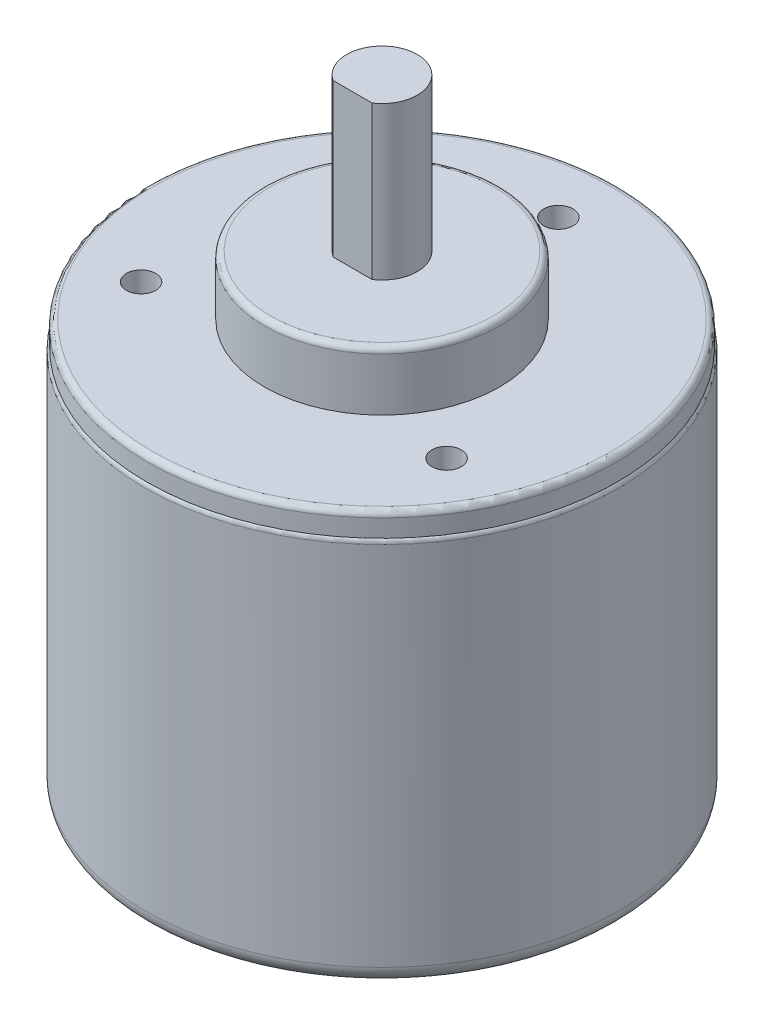
SolidWorks part; units mm, degrees
ref_plane "Front Plane" through (0, 0, 0) normal (0, 0, 1) x (1, 0, 0)
ref_plane "Top Plane" through (0, 0, 0) normal (0, 1, 0) x (1, 0, 0)
ref_plane "Right Plane" through (0, 0, 0) normal (1, 0, 0) x (0, 0, -1)
sketch "Sketch1" plane through (0, 0, 0) normal (0, 1, 0) x (1, 0, 0)
  circle A0 centre (0, 0) radius 20
  dimension "D1" = 40
extrude "Boss-Extrude1" add sketch "Sketch1" against normal blind 2
sketch "Sketch4" plane through (0, -2, 0) normal (0, -1, 0) x (1, 0, 0)
  circle A0 centre (0, 0) radius 20.15
  dimension "D1" = 40.3
extrude "Boss-Extrude3" add sketch "Sketch4" along normal blind 33
sketch "Sketch5" plane through (0, 0, 0) normal (0, 1, 0) x (1, 0, 0)
  circle A0 centre (0, 0) radius 10
  dimension "D1" = 20
extrude "Boss-Extrude4" add sketch "Sketch5" along normal blind 5
sketch "Sketch7" plane through (0, 5, 0) normal (0, 1, 0) x (1, 0, 0)
  line L1 (-1.6583, -2.5) -> (1.6583, -2.5)
  arc A1 (-1.6583, -2.5) -> (1.6583, -2.5) centre (0, 0) cw
  dimension "D1" = 3
  dimension "D2" = 2.5
extrude "Boss-Extrude5" add sketch "Sketch7" along normal blind 13
fillet "Fillet2" radius 0.5 3 edges at (0, -2, -20.15) (0, 5, 10) (0, 0, 20)
fillet "Fillet3" radius 1.5 1 edges at (0, -35, -20.15)
hole_wizard "M3x0.5 Tapped Hole1" positions "Sketch9" profile "Sketch8" tap size "M3x0.5" standard "ANSI Metric"
sketch "Sketch9" plane through (0, 0, 0) normal (0, 1, 0) x (1, 0, 0)
  circle A0 centre (0, 0) radius 15 construction
  circle A2 centre (0, 15) radius 1.3526 construction
  circle A3 centre (12.9904, -7.5) radius 1.3526 construction
  circle A4 centre (-12.9904, -7.5) radius 1.3526 construction
  point P7 (0, 15)
  point P22 (0, 0)
  point P31 (12.9904, -7.5)
  point P32 (-12.9904, -7.5)
  point P33 (0, 0)
  dimension "D1" = 30
  dimension "D2" = 3
  dimension "D3" = 3
sketch "Sketch8" plane through (0, 0, -15) normal (1, 0, 0) x (0, 0, 1)
  line L0 (0, 0) -> (0, 6.2511)
  line L1 (0, 6.2511) -> (1.25, 5.5)
  line L2 (1.25, 5.5) -> (1.25, 0)
  line L5 (1.25, 0) -> (0, 0)
  line L10 (0, 6.2511) -> (-1.25, 5.5) construction
  line L11 (0, -6.35) -> (0, 107.95) construction
  dimension "Tap Drill Dia." = 2.5
  dimension "Tap Drill Depth" = 5.5
  dimension "Drill Angle" = 118
cosmetic thread "Hole Thread1"
cosmetic thread "Hole Thread2"
cosmetic thread "Hole Thread3"
